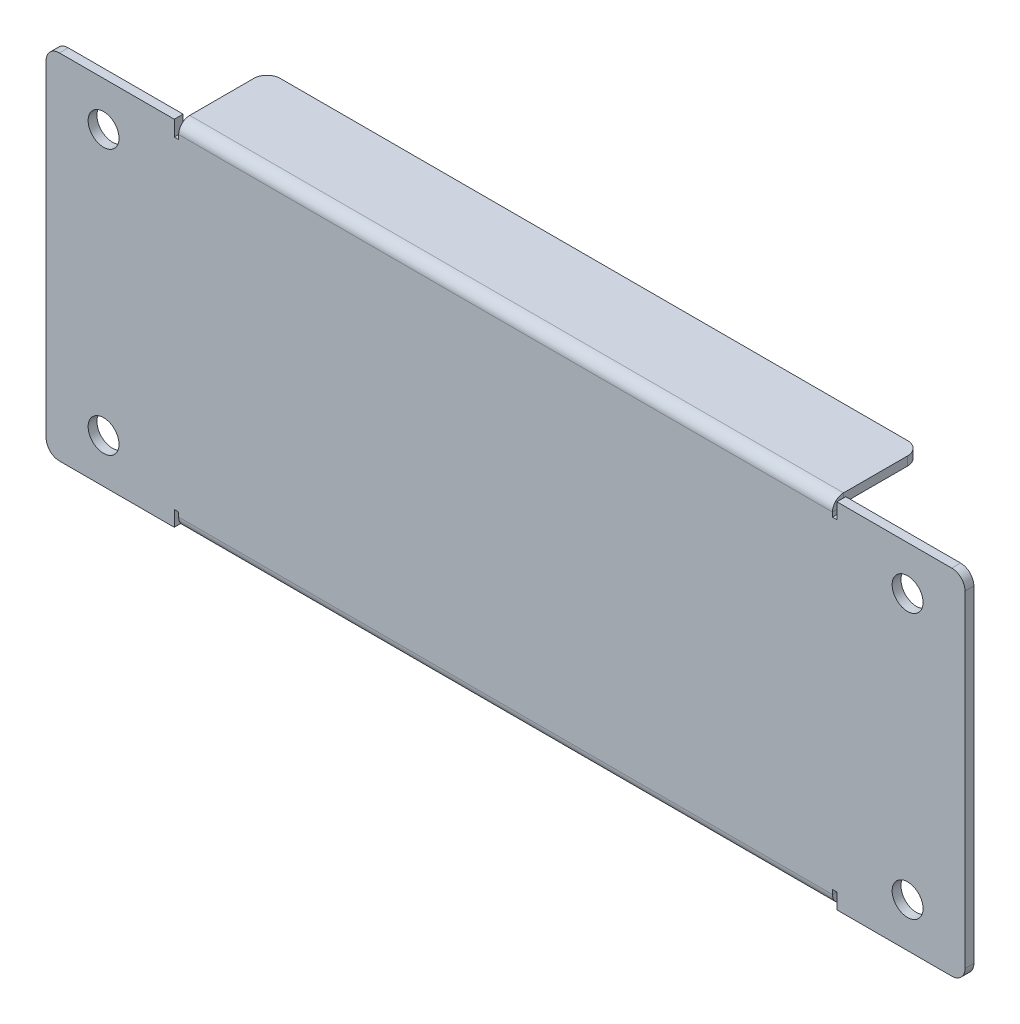
SolidWorks part; units mm, degrees
note: The reader was unsure of these and kept them because the rebuilt part matched: flange length of "边线-法兰1", "边线-法兰2".
ref_plane "前视基准面" through (0, 0, 0) normal (0, 0, 1) x (1, 0, 0)
ref_plane "上视基准面" through (0, 0, 0) normal (0, 1, 0) x (1, 0, 0)
ref_plane "右视基准面" through (0, 0, 0) normal (1, 0, 0) x (0, 0, -1)
sketch "草图1" plane through (0, 0, 0) normal (0, 0, 1) x (1, 0, 0)
  line L1 (-104, 40) -> (104, 40)
  line L2 (-104, 40) -> (-104, -40)
  line L3 (-104, -40) -> (104, -40)
  line L4 (104, 40) -> (104, -40)
  line L5 (-104, 40) -> (104, -40) construction
  line L6 (-104, -40) -> (104, 40) construction
  point P0 (0, 0)
  dimension "D1" = 208
  dimension "D2" = 80
sheet metal parameters "钣金1" thickness 2 parameters "D1"=0.5
base flange "基体-法兰1" sketch "草图1" thickness 2 reverse thickness direction no parameters "D1"=0.5
edge flange "边线-法兰1" sketch "草图5" flange angle 90 flange length 20 flange position material inside bend radius 0.5 thickness 2 relief rectangular parameters "D6"=10
sketch "草图5" plane through (0, 40, -2) normal (0, 1, 0) x (1, 0, 0)
  line L0 (104, 0) -> (-104, 0) construction
  line L1 (74, 0) -> (-74, 0)
  line L2 (-74, 0) -> (-74, 18)
  line L3 (-74, 18) -> (74, 18)
  line L4 (74, 18) -> (74, 0)
  line L6 (0, -2) -> (0, 42.0423) construction
  line L7 (104, -2) -> (-104, -2) construction
  dimension "D1" = 148
  dimension "D2" = 20
bend "边线折弯1" bend radius 0.5 bend angle 90 parameters "D5"=1
edge flange "边线-法兰2" sketch "草图8" flange angle 90 flange length 20 flange position material inside bend radius 0.5 thickness 2 relief rectangular parameters "D6"=10
sketch "草图8" plane through (0, -40, -2) normal (0, -1, 0) x (-1, 0, 0)
  line L2 (-74, 0) -> (-74, 18)
  line L3 (-74, 18) -> (74, 18)
  line L4 (74, 18) -> (74, 0)
  line L5 (104, 0) -> (-104, 0) construction
  line L6 (74, 0) -> (-74, 0)
  line L7 (0, 0) -> (0, 33.5665) construction
  line L8 (104, -2) -> (-104, -2) construction
  dimension "D1" = 148
  dimension "D2" = 20
bend "边线折弯2" bend radius 0.5 bend angle 90 parameters "D5"=2
sketch "草图10" plane through (0, 0, 0) normal (0, 0, 1) x (1, 0, 0)
  line L1 (91, -30) -> (-91, -30) construction
  line L2 (91, -30) -> (91, 30) construction
  line L3 (91, 30) -> (-91, 30) construction
  line L4 (-91, -30) -> (-91, 30) construction
  line L5 (91, -30) -> (-91, 30) construction
  line L6 (91, 30) -> (-91, -30) construction
  circle A0 centre (91, -30) radius 3.5
  circle A1 centre (91, 30) radius 3.5
  circle A2 centre (-91, -30) radius 3.5
  circle A3 centre (-91, 30) radius 3.5
  point P0 (0, 0)
  dimension "D3" = 7
  dimension "D1" = 182
  dimension "D2" = 60
extrude "切除-拉伸1" cut sketch "草图10" against normal through all normal cut yes
fillet "圆角1" radius 3 8 edges at (-74, -39, -20) (-104, -40, -1) (-104, 40, -1) (-74, 39, -20) (74, 39, -20) (104, 40, -1) (74, -39, -20) (104, -40, -1)
flat pattern "平板型式1" [suppressed]
sketch "折弯-线1" plane through (0, 0, 0) normal (0, 1, 0) x (-1, 0, 0)
bend of the flat pattern "展开-<边线折弯1>1"
bend of the flat pattern "展开-<边线折弯2>1"
